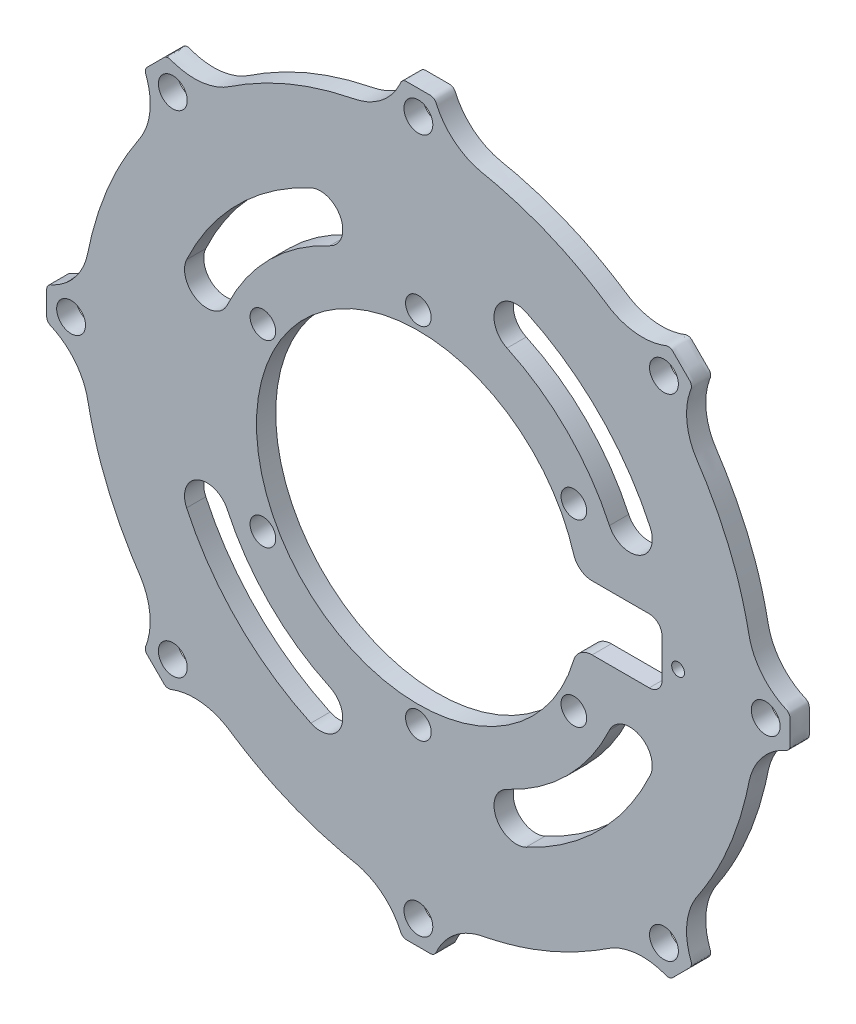
SolidWorks part; units mm, degrees
material "7075-T6, Plate (SS)"
ref_plane "Front Plane" through (0, 0, 0) normal (0, 0, 1) x (1, 0, 0)
ref_plane "Top Plane" through (0, 0, 0) normal (0, 1, 0) x (1, 0, 0)
ref_plane "Right Plane" through (0, 0, 0) normal (1, 0, 0) x (0, 0, -1)
sketch "Sketch1" plane through (0, 0, 0) normal (0, 0, 1) x (1, 0, 0)
  line L0 (0, 0) -> (15.2936, 32.9713) construction
  line L1 (-3.9972, 40.3023) -> (0, 28) construction
  line L3 (38, -3) -> (38, 3) construction
  line L4 (38, -3) -> (38, 3)
  line L5 (36, 5) -> (27.0936, 5)
  line L6 (36, -5) -> (27.0936, -5)
  line L7 (0, 0) -> (0, 48) construction
  line L8 (-2.8952, 57.0706) -> (-2.7624, 57.363)
  line L9 (-1.8466, 57.9614) -> (1.8466, 57.9614) construction
  line L10 (2.7624, 57.363) -> (2.7753, 57.3336)
  line L11 (-5, 52.2614) -> (5, 52.2614) construction
  line L12 (39.6791, 42.2906) -> (42.2906, 39.6791) construction
  line L13 (38.5785, 42.5034) -> (38.6085, 42.5151) construction
  line L14 (42.5151, 38.6085) -> (42.5034, 38.5785) construction
  line L15 (57.9614, 1.8466) -> (57.9614, -1.8466) construction
  line L16 (57.3336, 2.7753) -> (57.363, 2.7624) construction
  line L17 (57.363, -2.7624) -> (57.3336, -2.7753) construction
  line L18 (42.2906, -39.6791) -> (39.6791, -42.2906) construction
  line L19 (42.5034, -38.5785) -> (42.5151, -38.6085) construction
  line L20 (38.6085, -42.5151) -> (38.5785, -42.5034) construction
  line L21 (1.8466, -57.9614) -> (-1.8466, -57.9614) construction
  line L22 (2.7753, -57.3336) -> (2.7624, -57.363) construction
  line L23 (-2.7624, -57.363) -> (-2.7753, -57.3336) construction
  line L24 (-39.6791, -42.2906) -> (-42.2906, -39.6791) construction
  line L25 (-38.5785, -42.5034) -> (-38.6085, -42.5151) construction
  line L26 (-42.5151, -38.6085) -> (-42.5034, -38.5785) construction
  line L27 (-57.9614, -1.8466) -> (-57.9614, 1.8466) construction
  line L28 (-57.3336, -2.7753) -> (-57.363, -2.7624) construction
  line L29 (-57.363, 2.7624) -> (-57.3336, 2.7753) construction
  line L30 (-42.2906, 39.6791) -> (-39.6791, 42.2906) construction
  line L31 (-42.5034, 38.5785) -> (-42.5151, 38.6085) construction
  line L32 (-38.6085, 42.5151) -> (-38.5785, 42.5034) construction
  line L33 (0, 0) -> (25.7002, 25.7002) construction
  arc A0 (-10.0239, 51.5342) -> (-29.3522, 43.5281) centre (0, 0) ccw construction
  circle A1 centre (0, 0) radius 28 construction
  arc A3 (24.2164, 7.1504) -> (24.2164, -7.1504) centre (0, 0) ccw
  arc A4 (38, 3) -> (34, 3) centre (36, 3) ccw construction
  arc A5 (34, -3) -> (38, -3) centre (36, -3) ccw construction
  arc A6 (36, -5) -> (38, -3) centre (36, -3) ccw
  arc A7 (38, 3) -> (36, 5) centre (36, 3) ccw
  arc A8 (27.0936, -5) -> (24.2164, -7.1504) centre (27.0936, -8) ccw
  arc A9 (27.0936, 5) -> (24.2164, 7.1504) centre (27.0936, 8) cw
  circle A10 centre (0, 0) radius 36.3456 construction
  arc A13 (15.2936, 32.9713) -> (32.9713, 15.2936) centre (0, 0) cw construction
  circle A72 centre (0, 0) radius 40.5 construction
  circle A81 centre (40.4993, -0.2374) radius 1
  arc A104 (-2.8952, 57.0706) -> (-10.0239, 51.5342) centre (-11.9332, 61.3502) cw construction
  arc A105 (2.7753, 57.3336) -> (10.0239, 51.5342) centre (11.9332, 61.3502) ccw construction
  arc A106 (38.5785, 42.5034) -> (29.3522, 43.5281) centre (34.9431, 51.8192) cw construction
  arc A107 (42.5034, 38.5785) -> (43.5281, 29.3522) centre (51.8192, 34.9431) ccw construction
  arc A108 (57.3336, 2.7753) -> (51.5342, 10.0239) centre (61.3502, 11.9332) cw construction
  arc A109 (57.3336, -2.7753) -> (51.5342, -10.0239) centre (61.3502, -11.9332) ccw construction
  arc A110 (42.5034, -38.5785) -> (43.5281, -29.3522) centre (51.8192, -34.9431) cw construction
  arc A111 (38.5785, -42.5034) -> (29.3522, -43.5281) centre (34.9431, -51.8192) ccw construction
  arc A112 (2.7753, -57.3336) -> (10.0239, -51.5342) centre (11.9332, -61.3502) cw construction
  arc A113 (-2.7753, -57.3336) -> (-10.0239, -51.5342) centre (-11.9332, -61.3502) ccw construction
  arc A114 (-38.5785, -42.5034) -> (-29.3522, -43.5281) centre (-34.9431, -51.8192) cw construction
  arc A115 (-42.5034, -38.5785) -> (-43.5281, -29.3522) centre (-51.8192, -34.9431) ccw construction
  arc A116 (-57.3336, -2.7753) -> (-51.5342, -10.0239) centre (-61.3502, -11.9332) cw construction
  arc A117 (-57.3336, 2.7753) -> (-51.5342, 10.0239) centre (-61.3502, 11.9332) ccw construction
  arc A118 (-42.5034, 38.5785) -> (-43.5281, 29.3522) centre (-51.8192, 34.9431) cw construction
  arc A119 (-38.5785, 42.5034) -> (-29.3522, 43.5281) centre (-34.9431, 51.8192) ccw construction
  arc A120 (29.3522, 43.5281) -> (10.0239, 51.5342) centre (0, 0) ccw construction
  arc A121 (51.5342, 10.0239) -> (43.5281, 29.3522) centre (0, 0) ccw construction
  arc A122 (10.0239, -51.5342) -> (29.3522, -43.5281) centre (0, 0) ccw construction
  arc A123 (43.5281, -29.3522) -> (51.5342, -10.0239) centre (0, 0) ccw construction
  arc A124 (-29.3522, -43.5281) -> (-10.0239, -51.5342) centre (0, 0) ccw construction
  arc A125 (-51.5342, -10.0239) -> (-43.5281, -29.3522) centre (0, 0) ccw construction
  arc A126 (-43.5281, 29.3522) -> (-51.5342, 10.0239) centre (0, 0) ccw construction
  arc A127 (1.8466, 57.9614) -> (2.7624, 57.363) centre (1.8466, 56.9614) cw construction
  arc A128 (-2.7624, 57.363) -> (-1.8466, 57.9614) centre (-1.8466, 56.9614) cw construction
  arc A129 (-42.2906, 39.6791) -> (-42.5151, 38.6085) centre (-41.5835, 38.972) ccw construction
  arc A130 (-39.6791, 42.2906) -> (-38.6085, 42.5151) centre (-38.972, 41.5835) cw construction
  arc A131 (-57.9614, 1.8466) -> (-57.363, 2.7624) centre (-56.9614, 1.8466) cw construction
  arc A132 (-57.9614, -1.8466) -> (-57.363, -2.7624) centre (-56.9614, -1.8466) ccw construction
  arc A133 (-42.2906, -39.6791) -> (-42.5151, -38.6085) centre (-41.5835, -38.972) cw construction
  arc A134 (-39.6791, -42.2906) -> (-38.6085, -42.5151) centre (-38.972, -41.5835) ccw construction
  arc A135 (-1.8466, -57.9614) -> (-2.7624, -57.363) centre (-1.8466, -56.9614) cw construction
  arc A136 (1.8466, -57.9614) -> (2.7624, -57.363) centre (1.8466, -56.9614) ccw construction
  arc A137 (42.2906, -39.6791) -> (42.5151, -38.6085) centre (41.5835, -38.972) ccw construction
  arc A138 (39.6791, -42.2906) -> (38.6085, -42.5151) centre (38.972, -41.5835) cw construction
  arc A139 (57.9614, -1.8466) -> (57.363, -2.7624) centre (56.9614, -1.8466) cw construction
  arc A140 (57.9614, 1.8466) -> (57.363, 2.7624) centre (56.9614, 1.8466) ccw construction
  arc A141 (42.2906, 39.6791) -> (42.5151, 38.6085) centre (41.5835, 38.972) cw construction
  arc A142 (39.6791, 42.2906) -> (38.6085, 42.5151) centre (38.972, 41.5835) ccw construction
  arc A143 (36.1463, 16.7664) -> (16.7664, 36.1463) centre (0, 0) ccw
  arc A144 (29.7962, 13.8209) -> (13.8209, 29.7962) centre (0, 0) ccw
  arc A145 (29.7962, 13.8209) -> (36.1463, 16.7664) centre (32.9713, 15.2936) ccw
  arc A146 (16.7664, 36.1463) -> (13.8209, 29.7962) centre (15.2936, 32.9713) ccw
  arc A147 (32.9713, -15.2936) -> (15.2936, -32.9713) centre (0, 0) cw construction
  arc A148 (16.7664, -36.1463) -> (36.1463, -16.7664) centre (0, 0) ccw
  arc A149 (13.8209, -29.7962) -> (29.7962, -13.8209) centre (0, 0) ccw
  arc A150 (13.8209, -29.7962) -> (16.7664, -36.1463) centre (15.2936, -32.9713) ccw
  arc A151 (36.1463, -16.7664) -> (29.7962, -13.8209) centre (32.9713, -15.2936) ccw
  arc A152 (-15.2936, -32.9713) -> (-32.9713, -15.2936) centre (0, 0) cw construction
  arc A153 (-36.1463, -16.7664) -> (-16.7664, -36.1463) centre (0, 0) ccw
  arc A154 (-29.7962, -13.8209) -> (-13.8209, -29.7962) centre (0, 0) ccw
  arc A155 (-29.7962, -13.8209) -> (-36.1463, -16.7664) centre (-32.9713, -15.2936) ccw
  arc A156 (-16.7664, -36.1463) -> (-13.8209, -29.7962) centre (-15.2936, -32.9713) ccw
  arc A157 (-32.9713, 15.2936) -> (-15.2936, 32.9713) centre (0, 0) cw construction
  arc A158 (-16.7664, 36.1463) -> (-36.1463, 16.7664) centre (0, 0) ccw
  arc A159 (-13.8209, 29.7962) -> (-29.7962, 13.8209) centre (0, 0) ccw
  arc A160 (-13.8209, 29.7962) -> (-16.7664, 36.1463) centre (-15.2936, 32.9713) ccw
  arc A161 (-36.1463, 16.7664) -> (-29.7962, 13.8209) centre (-32.9713, 15.2936) ccw
  spline S0 degree 3 poles (-2.8952, 57.0706) (-3.9074, 54.9332) (-5.5869, 53.2683) (-7.7332, 52.275) (-8.2182, 52.0505) (-9.2243, 51.6793) (-10.8147, 51.3824) (-11.8574, 51.1462) (-12.3768, 51.0202) (-17.6601, 49.7386) (-22.6829, 47.6581) (-27.3251, 44.8285) (-27.7814, 44.5503) (-28.6857, 43.98) (-30.0203, 43.0653) (-30.9941, 42.6164) (-31.4958, 42.4322) (-33.8095, 41.5825) (-36.2742, 41.6063) (-38.571, 42.5005) (-38.5718, 42.5008) (-38.5735, 42.5015) (-38.576, 42.5025) (-38.5777, 42.5031) (-38.5785, 42.5034) (-38.5793, 42.5038) (-38.581, 42.5044) (-38.5835, 42.5054) (-38.5852, 42.506) (-38.586, 42.5064) (-38.591, 42.5083) (-38.596, 42.5102) (-38.601, 42.5122) (-38.6018, 42.5125) (-38.6035, 42.5132) (-38.606, 42.5141) (-38.6076, 42.5148) (-38.6085, 42.5151) (-38.6093, 42.5154) (-38.611, 42.5161) (-38.6135, 42.5171) (-38.6151, 42.5177) (-38.616, 42.518) (-38.8925, 42.6234) (-39.1877, 42.6038) (-39.4479, 42.463) (-39.4761, 42.4478) (-39.531, 42.4146) (-39.6111, 42.3586) (-39.6564, 42.3133) (-39.6791, 42.2906) (-39.7018, 42.268) (-39.7471, 42.2227) (-39.815, 42.1547) (-39.8603, 42.1094) (-39.883, 42.0867) (-40.6176, 41.3522) (-41.3522, 40.6176) (-42.0867, 39.883) (-42.1094, 39.8603) (-42.1547, 39.815) (-42.2227, 39.7471) (-42.268, 39.7018) (-42.2906, 39.6791) (-42.3133, 39.6564) (-42.3586, 39.6111) (-42.4146, 39.531) (-42.4478, 39.4761) (-42.463, 39.4479) (-42.6038, 39.1877) (-42.6234, 38.8925) (-42.518, 38.616) (-42.5177, 38.6151) (-42.5171, 38.6135) (-42.5161, 38.611) (-42.5154, 38.6093) (-42.5151, 38.6085) (-42.5148, 38.6076) (-42.5141, 38.606) (-42.5132, 38.6035) (-42.5125, 38.6018) (-42.5122, 38.601) (-42.5102, 38.596) (-42.5083, 38.591) (-42.5064, 38.586) (-42.506, 38.5852) (-42.5054, 38.5835) (-42.5044, 38.581) (-42.5038, 38.5793) (-42.5034, 38.5785) (-42.5031, 38.5777) (-42.5025, 38.576) (-42.5015, 38.5735) (-42.5008, 38.5718) (-42.5005, 38.571) (-41.6063, 36.2742) (-41.5825, 33.8095) (-42.4322, 31.4958) (-42.6164, 30.9941) (-43.0653, 30.0203) (-43.98, 28.6857) (-44.5503, 27.7814) (-44.8285, 27.3251) (-47.6581, 22.6829) (-49.7386, 17.6601) (-51.0202, 12.3768) (-51.1462, 11.8574) (-51.3824, 10.8147) (-51.6793, 9.2243) (-52.0505, 8.2182) (-52.275, 7.7332) (-53.3102, 5.4963) (-55.0698, 3.7704) (-57.3262, 2.7786) (-57.327, 2.7782) (-57.3287, 2.7775) (-57.3311, 2.7764) (-57.3328, 2.7757) (-57.3336, 2.7753) (-57.3344, 2.775) (-57.336, 2.7743) (-57.3385, 2.7732) (-57.3401, 2.7725) (-57.341, 2.7721) (-57.3459, 2.77) (-57.3508, 2.7678) (-57.3557, 2.7657) (-57.3565, 2.7653) (-57.3581, 2.7646) (-57.3606, 2.7635) (-57.3622, 2.7628) (-57.363, 2.7624) (-57.3638, 2.7621) (-57.3655, 2.7613) (-57.3679, 2.7603) (-57.3696, 2.7595) (-57.3704, 2.7592) (-57.6404, 2.6381) (-57.8354, 2.4156) (-57.9198, 2.132) (-57.9289, 2.1013) (-57.9443, 2.039) (-57.9614, 1.9428) (-57.9614, 1.8787) (-57.9614, 1.8466) (-57.9614, 1.8146) (-57.9614, 1.7505) (-57.9614, 1.6544) (-57.9614, 1.5903) (-57.9614, 1.5583) (-57.9614, 0.5194) (-57.9614, -0.5194) (-57.9614, -1.5583) (-57.9614, -1.5903) (-57.9614, -1.6544) (-57.9614, -1.7505) (-57.9614, -1.8146) (-57.9614, -1.8466) (-57.9614, -1.8787) (-57.9614, -1.9428) (-57.9443, -2.039) (-57.9289, -2.1013) (-57.9198, -2.132) (-57.8354, -2.4156) (-57.6404, -2.6381) (-57.3704, -2.7592) (-57.3696, -2.7595) (-57.3679, -2.7603) (-57.3655, -2.7613) (-57.3638, -2.7621) (-57.363, -2.7624) (-57.3622, -2.7628) (-57.3606, -2.7635) (-57.3581, -2.7646) (-57.3565, -2.7653) (-57.3557, -2.7657) (-57.3508, -2.7678) (-57.3459, -2.77) (-57.341, -2.7721) (-57.3401, -2.7725) (-57.3385, -2.7732) (-57.336, -2.7743) (-57.3344, -2.775) (-57.3336, -2.7753) (-57.3328, -2.7757) (-57.3311, -2.7764) (-57.3287, -2.7775) (-57.327, -2.7782) (-57.3262, -2.7786) (-55.0698, -3.7704) (-53.3102, -5.4963) (-52.275, -7.7332) (-52.0505, -8.2182) (-51.6793, -9.2243) (-51.3824, -10.8147) (-51.1462, -11.8574) (-51.0202, -12.3768) (-49.7386, -17.6601) (-47.6581, -22.6829) (-44.8285, -27.3251) (-44.5503, -27.7814) (-43.98, -28.6857) (-43.0653, -30.0203) (-42.6164, -30.9941) (-42.4322, -31.4958) (-41.5825, -33.8095) (-41.6063, -36.2742) (-42.5005, -38.571) (-42.5008, -38.5718) (-42.5015, -38.5735) (-42.5025, -38.576) (-42.5031, -38.5777) (-42.5034, -38.5785) (-42.5038, -38.5793) (-42.5044, -38.581) (-42.5054, -38.5835) (-42.506, -38.5852) (-42.5064, -38.586) (-42.5083, -38.591) (-42.5102, -38.596) (-42.5122, -38.601) (-42.5125, -38.6018) (-42.5132, -38.6035) (-42.5141, -38.606) (-42.5148, -38.6076) (-42.5151, -38.6085) (-42.5154, -38.6093) (-42.5161, -38.611) (-42.5171, -38.6135) (-42.5177, -38.6151) (-42.518, -38.616) (-42.6234, -38.8925) (-42.6038, -39.1877) (-42.463, -39.4479) (-42.4478, -39.4761) (-42.4146, -39.531) (-42.3586, -39.6111) (-42.3133, -39.6564) (-42.2906, -39.6791) (-42.268, -39.7018) (-42.2227, -39.7471) (-42.1547, -39.815) (-42.1094, -39.8603) (-42.0867, -39.883) (-41.3522, -40.6176) (-40.6176, -41.3522) (-39.883, -42.0867) (-39.8603, -42.1094) (-39.815, -42.1547) (-39.7471, -42.2227) (-39.7018, -42.268) (-39.6791, -42.2906) (-39.6564, -42.3133) (-39.6111, -42.3586) (-39.531, -42.4146) (-39.4761, -42.4478) (-39.4479, -42.463) (-39.1877, -42.6038) (-38.8925, -42.6234) (-38.616, -42.518) (-38.6151, -42.5177) (-38.6135, -42.5171) (-38.611, -42.5161) (-38.6093, -42.5154) (-38.6085, -42.5151) (-38.6076, -42.5148) (-38.606, -42.5141) (-38.6035, -42.5132) (-38.6018, -42.5125) (-38.601, -42.5122) (-38.596, -42.5102) (-38.591, -42.5083) (-38.586, -42.5064) (-38.5852, -42.506) (-38.5835, -42.5054) (-38.581, -42.5044) (-38.5793, -42.5038) (-38.5785, -42.5034) (-38.5777, -42.5031) (-38.576, -42.5025) (-38.5735, -42.5015) (-38.5718, -42.5008) (-38.571, -42.5005) (-36.2742, -41.6063) (-33.8095, -41.5825) (-31.4958, -42.4322) (-30.9941, -42.6164) (-30.0203, -43.0653) (-28.6857, -43.98) (-27.7814, -44.5503) (-27.3251, -44.8285) (-22.6829, -47.6581) (-17.6601, -49.7386) (-12.3768, -51.0202) (-11.8574, -51.1462) (-10.8147, -51.3824) (-9.2243, -51.6793) (-8.2182, -52.0505) (-7.7332, -52.275) (-5.4963, -53.3102) (-3.7704, -55.0698) (-2.7786, -57.3262) (-2.7782, -57.327) (-2.7775, -57.3287) (-2.7764, -57.3311) (-2.7757, -57.3328) (-2.7753, -57.3336) (-2.775, -57.3344) (-2.7743, -57.336) (-2.7732, -57.3385) (-2.7725, -57.3401) (-2.7721, -57.341) (-2.77, -57.3459) (-2.7678, -57.3508) (-2.7657, -57.3557) (-2.7653, -57.3565) (-2.7646, -57.3581) (-2.7635, -57.3606) (-2.7628, -57.3622) (-2.7624, -57.363) (-2.7621, -57.3638) (-2.7613, -57.3655) (-2.7603, -57.3679) (-2.7595, -57.3696) (-2.7592, -57.3704) (-2.6381, -57.6404) (-2.4156, -57.8354) (-2.132, -57.9198) (-2.1013, -57.9289) (-2.039, -57.9443) (-1.9428, -57.9614) (-1.8787, -57.9614) (-1.8466, -57.9614) (-1.8146, -57.9614) (-1.7505, -57.9614) (-1.6544, -57.9614) (-1.5903, -57.9614) (-1.5583, -57.9614) (-0.5194, -57.9614) (0.5194, -57.9614) (1.5583, -57.9614) (1.5903, -57.9614) (1.6544, -57.9614) (1.7505, -57.9614) (1.8146, -57.9614) (1.8466, -57.9614) (1.8787, -57.9614) (1.9428, -57.9614) (2.039, -57.9443) (2.1013, -57.9289) (2.132, -57.9198) (2.4156, -57.8354) (2.6381, -57.6404) (2.7592, -57.3704) (2.7595, -57.3696) (2.7603, -57.3679) (2.7613, -57.3655) (2.7621, -57.3638) (2.7624, -57.363) (2.7628, -57.3622) (2.7635, -57.3606) (2.7646, -57.3581) (2.7653, -57.3565) (2.7657, -57.3557) (2.7678, -57.3508) (2.77, -57.3459) (2.7721, -57.341) (2.7725, -57.3401) (2.7732, -57.3385) (2.7743, -57.336) (2.775, -57.3344) (2.7753, -57.3336) (2.7757, -57.3328) (2.7764, -57.3311) (2.7775, -57.3287) (2.7782, -57.327) (2.7786, -57.3262) (3.7704, -55.0698) (5.4963, -53.3102) (7.7332, -52.275) (8.2182, -52.0505) (9.2243, -51.6793) (10.8147, -51.3824) (11.8574, -51.1462) (12.3768, -51.0202) (17.6601, -49.7386) (22.6829, -47.6581) (27.3251, -44.8285) (27.7814, -44.5503) (28.6857, -43.98) (30.0203, -43.0653) (30.9941, -42.6164) (31.4958, -42.4322) (33.8095, -41.5825) (36.2742, -41.6063) (38.571, -42.5005) (38.5718, -42.5008) (38.5735, -42.5015) (38.576, -42.5025) (38.5777, -42.5031) (38.5785, -42.5034) (38.5793, -42.5038) (38.581, -42.5044) (38.5835, -42.5054) (38.5852, -42.506) (38.586, -42.5064) (38.591, -42.5083) (38.596, -42.5102) (38.601, -42.5122) (38.6018, -42.5125) (38.6035, -42.5132) (38.606, -42.5141) (38.6076, -42.5148) (38.6085, -42.5151) (38.6093, -42.5154) (38.611, -42.5161) (38.6135, -42.5171) (38.6151, -42.5177) (38.616, -42.518) (38.8925, -42.6234) (39.1877, -42.6038) (39.4479, -42.463) (39.4761, -42.4478) (39.531, -42.4146) (39.6111, -42.3586) (39.6564, -42.3133) (39.6791, -42.2906) (39.7018, -42.268) (39.7471, -42.2227) (39.815, -42.1547) (39.8603, -42.1094) (39.883, -42.0867) (40.6176, -41.3522) (41.3522, -40.6176) (42.0867, -39.883) (42.1094, -39.8603) (42.1547, -39.815) (42.2227, -39.7471) (42.268, -39.7018) (42.2906, -39.6791) (42.3133, -39.6564) (42.3586, -39.6111) (42.4146, -39.531) (42.4478, -39.4761) (42.463, -39.4479) (42.6038, -39.1877) (42.6234, -38.8925) (42.518, -38.616) (42.5177, -38.6151) (42.5171, -38.6135) (42.5161, -38.611) (42.5154, -38.6093) (42.5151, -38.6085) (42.5148, -38.6076) (42.5141, -38.606) (42.5132, -38.6035) (42.5125, -38.6018) (42.5122, -38.601) (42.5102, -38.596) (42.5083, -38.591) (42.5064, -38.586) (42.506, -38.5852) (42.5054, -38.5835) (42.5044, -38.581) (42.5038, -38.5793) (42.5034, -38.5785) (42.5031, -38.5777) (42.5025, -38.576) (42.5015, -38.5735) (42.5008, -38.5718) (42.5005, -38.571) (41.6063, -36.2742) (41.5825, -33.8095) (42.4322, -31.4958) (42.6164, -30.9941) (43.0653, -30.0203) (43.98, -28.6857) (44.5503, -27.7814) (44.8285, -27.3251) (47.6581, -22.6829) (49.7386, -17.6601) (51.0202, -12.3768) (51.1462, -11.8574) (51.3824, -10.8147) (51.6793, -9.2243) (52.0505, -8.2182) (52.275, -7.7332) (53.3102, -5.4963) (55.0698, -3.7704) (57.3262, -2.7786) (57.327, -2.7782) (57.3287, -2.7775) (57.3311, -2.7764) (57.3328, -2.7757) (57.3336, -2.7753) (57.3344, -2.775) (57.336, -2.7743) (57.3385, -2.7732) (57.3401, -2.7725) (57.341, -2.7721) (57.3459, -2.77) (57.3508, -2.7678) (57.3557, -2.7657) (57.3565, -2.7653) (57.3581, -2.7646) (57.3606, -2.7635) (57.3622, -2.7628) (57.363, -2.7624) (57.3638, -2.7621) (57.3655, -2.7613) (57.3679, -2.7603) (57.3696, -2.7595) (57.3704, -2.7592) (57.6404, -2.6381) (57.8354, -2.4156) (57.9198, -2.132) (57.9289, -2.1013) (57.9443, -2.039) (57.9614, -1.9428) (57.9614, -1.8787) (57.9614, -1.8466) (57.9614, -1.8146) (57.9614, -1.7505) (57.9614, -1.6544) (57.9614, -1.5903) (57.9614, -1.5583) (57.9614, -0.5194) (57.9614, 0.5194) (57.9614, 1.5583) (57.9614, 1.5903) (57.9614, 1.6544) (57.9614, 1.7505) (57.9614, 1.8146) (57.9614, 1.8466) (57.9614, 1.8787) (57.9614, 1.9428) (57.9443, 2.039) (57.9289, 2.1013) (57.9198, 2.132) (57.8354, 2.4156) (57.6404, 2.6381) (57.3704, 2.7592) (57.3696, 2.7595) (57.3679, 2.7603) (57.3655, 2.7613) (57.3638, 2.7621) (57.363, 2.7624) (57.3622, 2.7628) (57.3606, 2.7635) (57.3581, 2.7646) (57.3565, 2.7653) (57.3557, 2.7657) (57.3508, 2.7678) (57.3459, 2.77) (57.341, 2.7721) (57.3401, 2.7725) (57.3385, 2.7732) (57.336, 2.7743) (57.3344, 2.775) (57.3336, 2.7753) (57.3328, 2.7757) (57.3311, 2.7764) (57.3287, 2.7775) (57.327, 2.7782) (57.3262, 2.7786) (55.0698, 3.7704) (53.3102, 5.4963) (52.275, 7.7332) (52.0505, 8.2182) (51.6793, 9.2243) (51.3824, 10.8147) (51.1462, 11.8574) (51.0202, 12.3768) (49.7386, 17.6601) (47.6581, 22.6829) (44.8285, 27.3251) (44.5503, 27.7814) (43.98, 28.6857) (43.0653, 30.0203) (42.6164, 30.9941) (42.4322, 31.4958) (41.5825, 33.8095) (41.6063, 36.2742) (42.5005, 38.571) (42.5008, 38.5718) (42.5015, 38.5735) (42.5025, 38.576) (42.5031, 38.5777) (42.5034, 38.5785) (42.5038, 38.5793) (42.5044, 38.581) (42.5054, 38.5835) (42.506, 38.5852) (42.5064, 38.586) (42.5083, 38.591) (42.5102, 38.596) (42.5122, 38.601) (42.5125, 38.6018) (42.5132, 38.6035) (42.5141, 38.606) (42.5148, 38.6076) (42.5151, 38.6085) (42.5154, 38.6093) (42.5161, 38.611) (42.5171, 38.6135) (42.5177, 38.6151) (42.518, 38.616) (42.6234, 38.8925) (42.6038, 39.1877) (42.463, 39.4479) (42.4478, 39.4761) (42.4146, 39.531) (42.3586, 39.6111) (42.3133, 39.6564) (42.2906, 39.6791) (42.268, 39.7018) (42.2227, 39.7471) (42.1547, 39.815) (42.1094, 39.8603) (42.0867, 39.883) (41.3522, 40.6176) (40.6176, 41.3522) (39.883, 42.0867) (39.8603, 42.1094) (39.815, 42.1547) (39.7471, 42.2227) (39.7018, 42.268) (39.6791, 42.2906) (39.6564, 42.3133) (39.6111, 42.3586) (39.531, 42.4146) (39.4761, 42.4478) (39.4479, 42.463) (39.1877, 42.6038) (38.8925, 42.6234) (38.616, 42.518) (38.6151, 42.5177) (38.6135, 42.5171) (38.611, 42.5161) (38.6093, 42.5154) (38.6085, 42.5151) (38.6076, 42.5148) (38.606, 42.5141) (38.6035, 42.5132) (38.6018, 42.5125) (38.601, 42.5122) (38.596, 42.5102) (38.591, 42.5083) (38.586, 42.5064) (38.5852, 42.506) (38.5835, 42.5054) (38.581, 42.5044) (38.5793, 42.5038) (38.5785, 42.5034) (38.5777, 42.5031) (38.576, 42.5025) (38.5735, 42.5015) (38.5718, 42.5008) (38.571, 42.5005) (36.2742, 41.6063) (33.8095, 41.5825) (31.4958, 42.4322) (30.9941, 42.6164) (30.0203, 43.0653) (28.6857, 43.98) (27.7814, 44.5503) (27.3251, 44.8285) (22.6829, 47.6581) (17.6601, 49.7386) (12.3768, 51.0202) (11.8574, 51.1462) (10.8147, 51.3824) (9.2243, 51.6793) (8.2182, 52.0505) (7.7332, 52.275) (5.5869, 53.2683) (3.9074, 54.9332) (2.8952, 57.0706) (2.8663, 57.1317) (2.8097, 57.2544) (2.7303, 57.4441) (2.6534, 57.5561) (2.6097, 57.6076) (2.4833, 57.7569) (2.3195, 57.864) (2.132, 57.9198) (2.1013, 57.9289) (2.039, 57.9443) (1.9428, 57.9614) (1.8787, 57.9614) (1.8466, 57.9614) (1.8146, 57.9614) (1.7505, 57.9614) (1.6544, 57.9614) (1.5903, 57.9614) (1.5583, 57.9614) (0.5194, 57.9614) (-0.5194, 57.9614) (-1.5583, 57.9614) (-1.5903, 57.9614) (-1.6544, 57.9614) (-1.7505, 57.9614) (-1.8146, 57.9614) (-1.8466, 57.9614) (-1.8787, 57.9614) (-1.9428, 57.9614) (-2.039, 57.9443) (-2.1013, 57.9289) (-2.132, 57.9198) (-2.3195, 57.864) (-2.4833, 57.7569) (-2.6097, 57.6076) (-2.6534, 57.5561) (-2.7303, 57.4441) (-2.8097, 57.2544) (-2.8663, 57.1317) (-2.8952, 57.0706) (-3.9074, 54.9332) (-5.5869, 53.2683) knots -0.000551 0 0 0 0.018513 0.018513 0.018513 0.022871 0.027229 0.031586 0.031586 0.031586 0.07556 0.07556 0.07556 0.079917 0.084275 0.088632 0.088632 0.088632 0.107862 0.107862 0.107862 0.107869 0.107877 0.107884 0.107884 0.107884 0.107891 0.107898 0.107906 0.107906 0.107906 0.107949 0.107949 0.107949 0.107957 0.107964 0.107971 0.107971 0.107971 0.107979 0.107986 0.107993 0.107993 0.107993 0.110259 0.110259 0.110259 0.11052 0.110782 0.111043 0.111043 0.111043 0.111304 0.111565 0.111827 0.111827 0.111827 0.120297 0.120297 0.120297 0.120558 0.120819 0.12108 0.12108 0.12108 0.121342 0.121603 0.121864 0.121864 0.121864 0.12413 0.12413 0.12413 0.124137 0.124145 0.124152 0.124152 0.124152 0.124159 0.124166 0.124174 0.124174 0.124174 0.124217 0.124217 0.124217 0.124225 0.124232 0.124239 0.124239 0.124239 0.124247 0.124254 0.124261 0.124261 0.124261 0.143491 0.143491 0.143491 0.147848 0.152206 0.156564 0.156564 0.156564 0.200537 0.200537 0.200537 0.204894 0.209252 0.21361 0.21361 0.21361 0.232839 0.232839 0.232839 0.232847 0.232854 0.232861 0.232861 0.232861 0.232868 0.232876 0.232883 0.232883 0.232883 0.232927 0.232927 0.232927 0.232934 0.232941 0.232949 0.232949 0.232949 0.232956 0.232963 0.23297 0.23297 0.23297 0.235236 0.235236 0.235236 0.235498 0.235759 0.23602 0.23602 0.23602 0.236281 0.236543 0.236804 0.236804 0.236804 0.245274 0.245274 0.245274 0.245535 0.245796 0.246058 0.246058 0.246058 0.246319 0.24658 0.246841 0.246841 0.246841 0.249107 0.249107 0.249107 0.249115 0.249122 0.249129 0.249129 0.249129 0.249137 0.249144 0.249151 0.249151 0.249151 0.249195 0.249195 0.249195 0.249202 0.249209 0.249217 0.249217 0.249217 0.249224 0.249231 0.249238 0.249238 0.249238 0.268468 0.268468 0.268468 0.272826 0.277183 0.281541 0.281541 0.281541 0.325514 0.325514 0.325514 0.329872 0.334229 0.338587 0.338587 0.338587 0.357817 0.357817 0.357817 0.357824 0.357831 0.357839 0.357839 0.357839 0.357846 0.357853 0.35786 0.35786 0.35786 0.357904 0.357904 0.357904 0.357911 0.357919 0.357926 0.357926 0.357926 0.357933 0.35794 0.357948 0.357948 0.357948 0.360214 0.360214 0.360214 0.360475 0.360736 0.360997 0.360997 0.360997 0.361259 0.36152 0.361781 0.361781 0.361781 0.370251 0.370251 0.370251 0.370513 0.370774 0.371035 0.371035 0.371035 0.371296 0.371557 0.371819 0.371819 0.371819 0.374085 0.374085 0.374085 0.374092 0.374099 0.374107 0.374107 0.374107 0.374114 0.374121 0.374128 0.374128 0.374128 0.374172 0.374172 0.374172 0.374179 0.374187 0.374194 0.374194 0.374194 0.374201 0.374209 0.374216 0.374216 0.374216 0.393445 0.393445 0.393445 0.397803 0.402161 0.406518 0.406518 0.406518 0.450492 0.450492 0.450492 0.454849 0.459207 0.463564 0.463564 0.463564 0.482794 0.482794 0.482794 0.482801 0.482809 0.482816 0.482816 0.482816 0.482823 0.48283 0.482838 0.482838 0.482838 0.482881 0.482881 0.482881 0.482889 0.482896 0.482903 0.482903 0.482903 0.482911 0.482918 0.482925 0.482925 0.482925 0.485191 0.485191 0.485191 0.485452 0.485714 0.485975 0.485975 0.485975 0.486236 0.486497 0.486759 0.486759 0.486759 0.495229 0.495229 0.495229 0.49549 0.495751 0.496012 0.496012 0.496012 0.496274 0.496535 0.496796 0.496796 0.496796 0.499062 0.499062 0.499062 0.499069 0.499077 0.499084 0.499084 0.499084 0.499091 0.499098 0.499106 0.499106 0.499106 0.499149 0.499149 0.499149 0.499157 0.499164 0.499171 0.499171 0.499171 0.499179 0.499186 0.499193 0.499193 0.499193 0.518423 0.518423 0.518423 0.52278 0.527138 0.531496 0.531496 0.531496 0.575469 0.575469 0.575469 0.579826 0.584184 0.588542 0.588542 0.588542 0.607771 0.607771 0.607771 0.607779 0.607786 0.607793 0.607793 0.607793 0.6078 0.607808 0.607815 0.607815 0.607815 0.607859 0.607859 0.607859 0.607866 0.607873 0.607881 0.607881 0.607881 0.607888 0.607895 0.607902 0.607902 0.607902 0.610168 0.610168 0.610168 0.61043 0.610691 0.610952 0.610952 0.610952 0.611213 0.611475 0.611736 0.611736 0.611736 0.620206 0.620206 0.620206 0.620467 0.620728 0.62099 0.62099 0.62099 0.621251 0.621512 0.621773 0.621773 0.621773 0.624039 0.624039 0.624039 0.624047 0.624054 0.624061 0.624061 0.624061 0.624069 0.624076 0.624083 0.624083 0.624083 0.624127 0.624127 0.624127 0.624134 0.624141 0.624149 0.624149 0.624149 0.624156 0.624163 0.62417 0.62417 0.62417 0.6434 0.6434 0.6434 0.647758 0.652115 0.656473 0.656473 0.656473 0.700446 0.700446 0.700446 0.704804 0.709161 0.713519 0.713519 0.713519 0.732749 0.732749 0.732749 0.732756 0.732763 0.732771 0.732771 0.732771 0.732778 0.732785 0.732792 0.732792 0.732792 0.732836 0.732836 0.732836 0.732843 0.732851 0.732858 0.732858 0.732858 0.732865 0.732872 0.73288 0.73288 0.73288 0.735146 0.735146 0.735146 0.735407 0.735668 0.735929 0.735929 0.735929 0.736191 0.736452 0.736713 0.736713 0.736713 0.745183 0.745183 0.745183 0.745445 0.745706 0.745967 0.745967 0.745967 0.746228 0.746489 0.746751 0.746751 0.746751 0.749017 0.749017 0.749017 0.749024 0.749031 0.749039 0.749039 0.749039 0.749046 0.749053 0.74906 0.74906 0.74906 0.749104 0.749104 0.749104 0.749111 0.749119 0.749126 0.749126 0.749126 0.749133 0.74914 0.749148 0.749148 0.749148 0.768377 0.768377 0.768377 0.772735 0.777093 0.78145 0.78145 0.78145 0.825424 0.825424 0.825424 0.829781 0.834139 0.838496 0.838496 0.838496 0.857726 0.857726 0.857726 0.857733 0.857741 0.857748 0.857748 0.857748 0.857755 0.857762 0.85777 0.85777 0.85777 0.857813 0.857813 0.857813 0.857821 0.857828 0.857835 0.857835 0.857835 0.857843 0.85785 0.857857 0.857857 0.857857 0.860123 0.860123 0.860123 0.860384 0.860646 0.860907 0.860907 0.860907 0.861168 0.861429 0.86169 0.86169 0.86169 0.870161 0.870161 0.870161 0.870422 0.870683 0.870944 0.870944 0.870944 0.871206 0.871467 0.871728 0.871728 0.871728 0.873994 0.873994 0.873994 0.874001 0.874009 0.874016 0.874016 0.874016 0.874023 0.87403 0.874038 0.874038 0.874038 0.874081 0.874081 0.874081 0.874089 0.874096 0.874103 0.874103 0.874103 0.874111 0.874118 0.874125 0.874125 0.874125 0.893355 0.893355 0.893355 0.897712 0.90207 0.906428 0.906428 0.906428 0.950401 0.950401 0.950401 0.954758 0.959116 0.963474 0.963474 0.963474 0.981987 0.981987 0.981987 0.982538 0.983089 0.98364 0.98364 0.98364 0.985191 0.985191 0.985191 0.985452 0.985714 0.985975 0.985975 0.985975 0.986236 0.986497 0.986759 0.986759 0.986759 0.995229 0.995229 0.995229 0.99549 0.995751 0.996012 0.996012 0.996012 0.996274 0.996535 0.996796 0.996796 0.996796 0.998347 0.998347 0.998347 0.998898 0.999449 1 1 1 1.018513 1.018513 1.018513 weights 1 0.960139 0.960139 1 1 1 1 1 1 0.992037 0.992037 1 1 1 1 1 1 0.956887 0.956887 1 1 1 1 1 1 1 1 1 1 1 1 1 1 1 1 1 1 1 1 1 1 1 1 0.939305 0.939305 1 1 1 1 1 1 1 1 1 1 1 1 1 1 1 1 1 1 1 1 1 1 1 1 0.939305 0.939305 1 1 1 1 1 1 1 1 1 1 1 1 1 1 1 1 1 1 1 1 1 1 1 1 0.956887 0.956887 1 1 1 1 1 1 0.992037 0.992037 1 1 1 1 1 1 0.956887 0.956887 1 1 1 1 1 1 1 1 1 1 1 1 1 1 1 1 1 1 1 1 1 1 1 1 0.939305 0.939305 1 1 1 1 1 1 1 1 1 1 1 1 1 1 1 1 1 1 1 1 1 1 1 1 0.939305 0.939305 1 1 1 1 1 1 1 1 1 1 1 1 1 1 1 1 1 1 1 1 1 1 1 1 0.956887 0.956887 1 1 1 1 1 1 0.992037 0.992037 1 1 1 1 1 1 0.956887 0.956887 1 1 1 1 1 1 1 1 1 1 1 1 1 1 1 1 1 1 1 1 1 1 1 1 0.939305 0.939305 1 1 1 1 1 1 1 1 1 1 1 1 1 1 1 1 1 1 1 1 1 1 1 1 0.939305 0.939305 1 1 1 1 1 1 1 1 1 1 1 1 1 1 1 1 1 1 1 1 1 1 1 1 0.956887 0.956887 1 1 1 1 1 1 0.992037 0.992037 1 1 1 1 1 1 0.956887 0.956887 1 1 1 1 1 1 1 1 1 1 1 1 1 1 1 1 1 1 1 1 1 1 1 1 0.939305 0.939305 1 1 1 1 1 1 1 1 1 1 1 1 1 1 1 1 1 1 1 1 1 1 1 1 0.939305 0.939305 1 1 1 1 1 1 1 1 1 1 1 1 1 1 1 1 1 1 1 1 1 1 1 1 0.956887 0.956887 1 1 1 1 1 1 0.992037 0.992037 1 1 1 1 1 1 0.956887 0.956887 1 1 1 1 1 1 1 1 1 1 1 1 1 1 1 1 1 1 1 1 1 1 1 1 0.939305 0.939305 1 1 1 1 1 1 1 1 1 1 1 1 1 1 1 1 1 1 1 1 1 1 1 1 0.939305 0.939305 1 1 1 1 1 1 1 1 1 1 1 1 1 1 1 1 1 1 1 1 1 1 1 1 0.956887 0.956887 1 1 1 1 1 1 0.992037 0.992037 1 1 1 1 1 1 0.956887 0.956887 1 1 1 1 1 1 1 1 1 1 1 1 1 1 1 1 1 1 1 1 1 1 1 1 0.939305 0.939305 1 1 1 1 1 1 1 1 1 1 1 1 1 1 1 1 1 1 1 1 1 1 1 1 0.939305 0.939305 1 1 1 1 1 1 1 1 1 1 1 1 1 1 1 1 1 1 1 1 1 1 1 1 0.956887 0.956887 1 1 1 1 1 1 0.992037 0.992037 1 1 1 1 1 1 0.956887 0.956887 1 1 1 1 1 1 1 1 1 1 1 1 1 1 1 1 1 1 1 1 1 1 1 1 0.939305 0.939305 1 1 1 1 1 1 1 1 1 1 1 1 1 1 1 1 1 1 1 1 1 1 1 1 0.939305 0.939305 1 1 1 1 1 1 1 1 1 1 1 1 1 1 1 1 1 1 1 1 1 1 1 1 0.956887 0.956887 1 1 1 1 1 1 0.992037 0.992037 1 1 1 1 1 1 0.960139 0.960139 1 1 1 1 1 1 0.972283 0.972283 1 1 1 1 1 1 1 1 1 1 1 1 1 1 1 1 1 1 1 1 1 1 1 1 0.972283 0.972283 1 1 1 1 1 1 0.960139 0.960139 only from (-2.8952, 57.0706) to (-2.8952, 57.0706)
  point P4 (0, 28)
  point P5 (24.2487, 14)
  point P9 (24.2487, -14)
  point P10 (0, -28)
  point P11 (-24.2487, -14)
  point P12 (-24.2487, 14)
  point P13 (0, 0)
  point P29 (25.7002, 25.7002)
  point P44 (25.7002, -25.7002)
  point P51 (-25.7002, -25.7002)
  point P58 (-25.7002, 25.7002)
  point P63 (0, 0)
  point P154 (0, 0)
  point P157 (0, 48)
  point P216 (0, 0)
  point P228 (2.5, 57.9614)
  point P285 (0, 0)
  point P288 (-2.5, 57.9614)
  point P317 (38.2979, 38.2979)
  point P318 (0, 54.1614)
  point P319 (0, 24)
  point P320 (54.1614, 0)
  point P323 (38.2979, -38.2979)
  point P324 (0, -54.1614)
  point P325 (-38.2979, -38.2979)
  point P326 (-54.1614, 0)
  point P327 (-38.2979, 38.2979)
  point P328 (0, 0)
  dimension "D1" = 56
  dimension "D2" = 105
  dimension "D3" = 6
  dimension "D4" = 50.5
  dimension "D5" = 3
  dimension "D6" = 2
  dimension "D7" = 40.4993
  dimension "D8" = 0.2374
  dimension "D9" = 18
  dimension "81" = 81
  dimension "D10" = 3.5
  dimension "D13" = 5.7
  dimension "D16" = 10
  dimension "D19" = 1
  dimension "D20" = 1
  dimension "D12" = 48
  dimension "D14" = 5
  dimension "D15" = 10
  dimension "D18" = 3.8
  dimension "D21" = 8
  dimension "D11" = 25
  dimension "D22" = 45
  dimension "D17" = 8
  dimension "D23" = 4
extrude "Boss-Extrude1" add sketch "Sketch1" along normal blind 3 contours A0 A81 region at (-1.3507, 56.5044, 0)
hole_wizard "Ø4.0mm Dowel Hole1" positions "Sketch4" profile "Sketch5" hole size "Ø4.0" standard "ISO"
sketch "Sketch4" plane through (0, 0, 3) normal (0, 0, 1) x (1, 0, 0)
  point P0 (0, 28)
  point P3 (24.2487, 14)
  point P6 (24.2487, -14)
  point P9 (0, -28)
  point P12 (-24.2487, -14)
  point P15 (-24.2487, 14)
sketch "Sketch5" plane through (0, 28, 3) normal (1, 0, 0) x (0, -1, 0)
  line L0 (0, 0) -> (0, 5.2017)
  line L1 (0, 5.2017) -> (2, 4)
  line L2 (2, 4) -> (2, 0)
  line L5 (2, 0) -> (0, 0)
  line L10 (0, 5.2017) -> (-2, 4) construction
  line L11 (0, -6.35) -> (0, 107.95) construction
  dimension "Hole Dia." = 4
  dimension "Hole Depth" = 4
  dimension "Drill Angle" = 118
hole_wizard "M4 Clearance Hole1" positions "Sketch14" profile "Sketch15" hole size "M4" standard "ISO"
sketch "Sketch14" plane through (0, 0, 3) normal (0, 0, 1) x (1, 0, 0)
  point P0 (0, 54.1614)
  point P3 (-38.2979, 38.2979)
  point P6 (38.2979, 38.2979)
  point P9 (54.1614, 0)
  point P12 (38.2979, -38.2979)
  point P15 (-54.1614, 0)
  point P18 (-38.2979, -38.2979)
  point P21 (0, -54.1614)
sketch "Sketch15" plane through (0, 54.1614, 3) normal (1, 0, 0) x (0, -1, 0)
  line L0 (0, 0) -> (0, 5.3519)
  line L1 (0, 5.3519) -> (2.25, 4)
  line L2 (2.25, 4) -> (2.25, 0)
  line L5 (2.25, 0) -> (0, 0)
  line L10 (0, 5.3519) -> (-2.25, 4) construction
  line L11 (0, -6.35) -> (0, 107.95) construction
  dimension "Hole Dia." = 4.5
  dimension "Hole Depth" = 4
  dimension "Drill Angle" = 118
